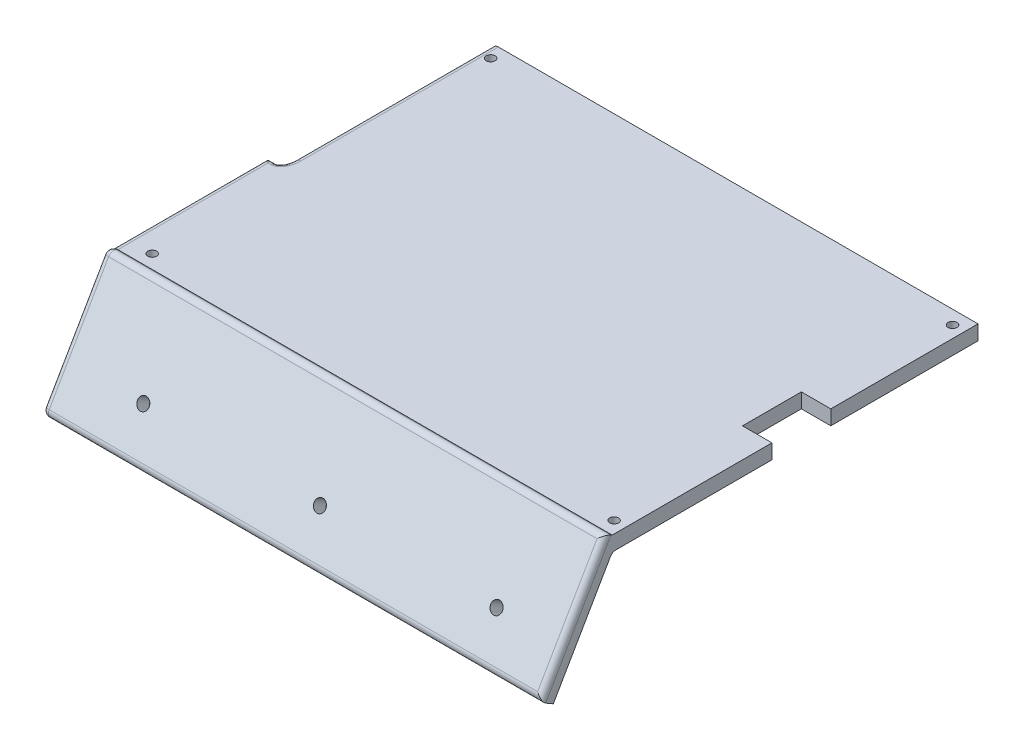
SolidWorks part; units mm, degrees
ref_plane "Front Plane" through (0, 0, 0) normal (0, 0, 1) x (1, 0, 0)
ref_plane "Top Plane" through (0, 0, 0) normal (0, 1, 0) x (1, 0, 0)
ref_plane "Right Plane" through (0, 0, 0) normal (1, 0, 0) x (0, 0, -1)
other "Configuration Table"
sketch "Sketch1" plane through (0, 0, 0) normal (0, 1, 0) x (1, 0, 0)
  line L0 (-105.0791, 0) -> (105.0791, 0) construction
  line L1 (82.45, -62.125) -> (-82.45, -62.125)
  line L2 (82.45, -62.125) -> (82.45, -7.875)
  line L3 (82.45, 62.125) -> (-82.45, 62.125)
  line L4 (-82.45, -62.125) -> (-82.45, 62.125)
  line L5 (82.45, -62.125) -> (-82.45, 62.125) construction
  line L6 (82.45, 62.125) -> (-82.45, -62.125) construction
  line L7 (0, -106.7771) -> (0, 106.7771) construction
  line L8 (82.45, 12.125) -> (82.45, 62.125)
  line L9 (82.45, 12.125) -> (72.45, 12.125)
  line L11 (82.45, -7.875) -> (72.45, -7.875)
  line L12 (72.45, 12.125) -> (72.45, -7.875)
  circle A0 centre (-78.45, 57.48) radius 1.5
  circle A4 centre (-78.45, -57.48) radius 1.5
  circle A5 centre (78.45, -57.48) radius 1.5
  circle A6 centre (78.45, 57.48) radius 1.5
  point P0 (0, 0)
  point P22 (72.45, 2.125)
  dimension "D3" = 3
  dimension "D1" = 156.9
  dimension "D2" = 114.96
  dimension "D4" = 124.25
  dimension "D5" = 164.9
  dimension "D6" = 20
  dimension "D7" = 60
  dimension "D8" = 10
extrude "Boss-Extrude1" add sketch "Sketch1" along normal blind 5
ref_plane "Plane1" through (0, -26.9009, 15.5313) normal (0, -0.866, 0.5) x (1, 0, 0)
sketch "Sketch2" plane through (0, -26.9009, 15.5313) normal (0, -0.866, 0.5) x (1, 0, 0)
  line L0 (-82.45, 53.8018) -> (82.45, 53.8018) construction
  line L1 (-82.45, 53.8018) -> (82.45, 53.8018)
  line L2 (-82.45, 53.8018) -> (-82.45, 58.8018)
  line L3 (-82.45, 58.8018) -> (82.45, 58.8018)
  line L4 (82.45, 53.8018) -> (82.45, 58.8018)
  line L5 (-82.45, -53.8018) -> (-82.45, 53.8018) construction
  point P6 (0, 53.8018)
  point P8 (-82.45, 53.8018)
  dimension "D1" = 5
extrude "Boss-Extrude2" add sketch "Sketch2" along normal blind 40 and the other way up to vertex (4.3301 mm away) other way up to point (82.45, 5, 62.125)
sketch "Sketch3" plane through (0, 0, 0) normal (1, 0, 0) x (0, 0, -1)
  line L0 (-64.625, -4.3301) -> (-42.9744, -16.8301)
  line L1 (-62.125, 0) -> (-82.125, -34.641) construction
  line L2 (-42.9744, -16.8301) -> (-13.8237, 0)
  line L3 (-62.125, 0) -> (-7.875, 0) construction
  line L4 (-62.125, 0) -> (-13.8237, 0)
  line L5 (-62.125, 0) -> (-64.625, -4.3301)
  point P4 (-43.4044, -17.5471)
  dimension "D1" = 25
  dimension "D2" = 35
  dimension "D3" = 120
extrude "Boss-Extrude3" add sketch "Sketch3" along normal blind 5 from offset 50
mirror "Mirror1" about plane through (0, 0, 0) normal (1, 0, 0) of "Boss-Extrude3"
extrude "Boss-Extrude4" add sketch "Sketch3<2>" along normal mid plane 5
sketch "Sketch3<2>" plane through (0, 0, 0) normal (1, 0, 0) x (0, 0, -1) same geometry as "Sketch3"
sketch "Sketch4" plane through (-82.45, 0, 0) normal (-1, 0, 0) x (0, 0, 1)
  line L0 (-62.125, 5) -> (62.125, 5) construction
  line L1 (5.6446, 5) -> (62.125, 5)
  line L2 (5.6446, 5) -> (64.8045, -44.641)
  line L3 (64.8045, -44.641) -> (86.4551, -32.141)
  line L4 (86.4551, -32.141) -> (82.125, -34.641) construction
  line L7 (62.125, 5) -> (64.2901, 6.25)
  line L8 (64.2901, 6.25) -> (86.4551, -32.141)
  circle A0 centre (61.6346, -29.1506) radius 1.985
  point P1 (0, 0)
  dimension "D3" = 3.97
  dimension "D1" = 25
  dimension "D2" = 110
  dimension "D4" = 20
  dimension "D5" = 15
extrude "Boss-Extrude5" add sketch "Sketch4" along normal blind 5
fillet "Fillet1" radius 2 30 edges at (-52.5, 0, 13.8237) (-50, 0, 37.9744) (-26.25, 0, 62.125) (-68.725, 0, 62.125) (26.25, 0, 62.125) (68.725, 0, 62.125) (-55, 0, 37.9744) (0, 0, 13.8237) (52.5, 0, 13.8237) (-2.5, 0, 37.9744) (50, 0, 37.9744) (2.5, 0, 37.9744) (55, 0, 37.9744) (-2.5, 6.25, 64.2901) (-84.95, 5, 5.6446) (-84.95, -44.641, 64.8045) (-82.45, 5, -28.2402) (-87.45, 5, 33.8848) (-82.45, 2.5, 8.624) (82.45, -12.9455, 75.3726) (-2.5, -32.141, 86.4551) (-87.45, -38.391, 75.6298) (-87.45, -12.9455, 75.3726) (-87.45, 5.625, 63.2075) (-50, -2.1651, 63.375) (-55, -2.1651, 63.375) (50, -2.1651, 63.375) (55, -2.1651, 63.375) (2.5, -2.1651, 63.375) (-2.5, -2.1651, 63.375)
sketch "Sketch5" plane through (0, 29.4009, 50.9239) normal (0, 0.5, 0.866) x (1, 0, 0)
  line L0 (-60, -56.0625) -> (60, -56.0625) construction
  line L2 (82.45, -71.0625) -> (-85.45, -71.0625) construction
  circle A0 centre (-60, -56.0625) radius 1.985
  circle A1 centre (0, -56.0625) radius 1.985
  circle A2 centre (60, -56.0625) radius 1.985
  point P6 (0, -56.0625)
  point P7 (0, 0)
  dimension "D1" = 3.97
  dimension "D2" = 120
  dimension "D3" = 15
extrude "Cut-Extrude1" cut sketch "Sketch5" against normal blind 5
